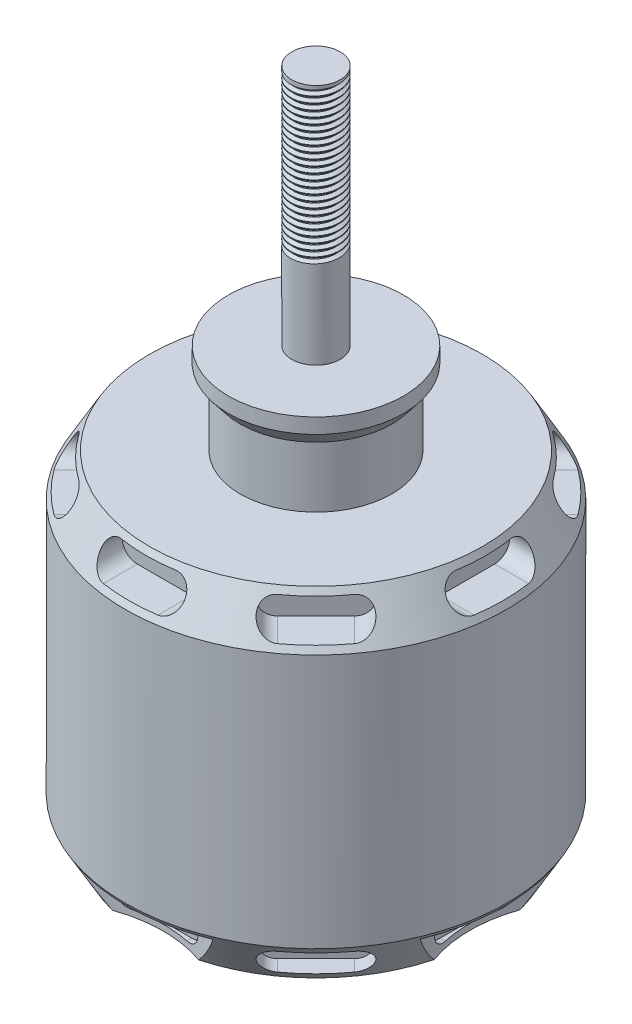
SolidWorks part; units mm, degrees
note: '?' marks a value the reader was unsure of.
ref_plane "Front Plane" through (0, 0, 0) normal (0, 0, 1) x (1, 0, 0)
ref_plane "Top Plane" through (0, 0, 0) normal (0, 1, 0) x (1, 0, 0)
ref_plane "Right Plane" through (0, 0, 0) normal (1, 0, 0) x (0, 0, -1)
sketch "Sketch1" plane through (0, 0, 0) normal (0, 1, 0) x (1, 0, 0)
  circle A0 centre (0, 0) radius 31.5
  dimension "D1" = 63
extrude "Boss-Extrude1" add sketch "Sketch1" along normal blind 40.7
ref_plane "Plane1" through (0, 47.7, 0) normal (0, 1, 0) x (1, 0, 0)
sketch "Sketch3" plane through (0, 47.7, 0) normal (0, 1, 0) x (1, 0, 0)
  circle A0 centre (0, 0) radius 27.5
  dimension "D1" = 55
loft "Loft1" add profiles "Sketch3" section "Sketch3" section edge at (0, 40.7, 31.5) connector at (-15.8974, 47.7, 22.4393) connector at (-17.8527, 40.7, 25.9525)
sketch "Sketch5" plane through (0, 47.7, 0) normal (0, 1, 0) x (1, 0, 0)
  circle A0 centre (0, 0) radius 12.5
  dimension "D1" = 25
extrude "Boss-Extrude2" add sketch "Sketch5" along normal blind 10
ref_plane "Plane3" through (0, 62.7, 0) normal (0, 1, 0) x (1, 0, 0)
sketch "Sketch8" plane through (0, 62.7, 0) normal (0, 1, 0) x (1, 0, 0)
  circle A0 centre (0, 0) radius 14.462
extrude "Boss-Extrude3" add sketch "Sketch8" against normal blind 2.5 separate body
loft "Loft3" add section edge at (0, 60.2, 14.462) section edge at (0, 57.7, 12.5) connector at (-8.5885, 60.2, 11.6356) connector at (-7.8828, 57.7, 9.7011)
sketch "Sketch9" plane through (0, 62.7, 0) normal (0, 1, 0) x (1, 0, 0)
  circle A0 centre (0, 0) radius 4
  dimension "D1" = 8
extrude "Boss-Extrude4" add sketch "Sketch9" along normal blind 40
thread "Thread1" pitch 1 method cut profile "Thread Profile1" start angle 0, offset 0, length 25, pitch 1, diameter 8
ref_plane "Plane4" through (-4, 102.7, 0) normal (0, 0, 1) x (-1, 0, 0)
sketch "Thread Profile1" plane through (-4, 102.7, 0) normal (0, 0, 1) x (-1, 0, 0)
  line L0 (0, 0) -> (0, 1) construction
  line L11 (0, 0) -> (0, 0.875)
  line L12 (0, 0.875) -> (-0.5413, 0.5625)
  line L13 (-0.5413, 0.5625) -> (-0.5413, 0.3125)
  line L15 (-0.5413, 0.3125) -> (0, 0)
  line L17 (-0.5413, 0.4375) -> (0, 0.4375) construction
  point P2 (0, 0)
  dimension "Pitch" = 1
  dimension "Profile_Angle" = 60
  dimension "Profile_Land" = 0.25
  dimension "Profile_Height" = 0.5413
sketch "Sketch17" plane through (0, 0, 0) normal (0, -1, 0) x (1, 0, 0)
  circle A0 centre (0, 0) radius 31.5
extrude "Boss-Extrude5" add sketch "Sketch17" along normal blind 1.3
ref_plane "Plane5" through (0, -8.3, 0) normal (0, -1, 0) x (-1, 0, 0)
sketch "Sketch18" plane through (0, -8.3, 0) normal (0, -1, 0) x (-1, 0, 0)
  circle A0 centre (0, 0) radius 27.5
  dimension "D1" = 55
loft "Loft4" add profiles "Sketch18" section "Sketch18" section edge at (0, -1.3, -31.5) connector at (25.19, -8.3, 11.0325) connector at (30.1075, -1.3, 9.2623)
sketch "Sketch20" plane through (0, -8.3, 0) normal (0, -1, 0) x (1, 0, 0)
  circle A0 centre (0, 0) radius 6.5
  dimension "D1" = 13
extrude "Boss-Extrude6" add sketch "Sketch20" along normal blind 0.75
sketch "Sketch21" plane through (0, -9.05, 0) normal (0, -1, 0) x (1, 0, 0)
  circle A0 centre (0, 0) radius 7
  dimension "D1" = 14
extrude "Boss-Extrude7" add sketch "Sketch21" along normal blind 5.55
sketch "Sketch23" plane through (0, -8.3, 0) normal (0, -1, 0) x (1, 0, 0)
  line L0 (0, 27.5) -> (0, -27.5) construction
  circle A0 centre (0, 0) radius 22 construction
  circle A1 centre (0, 0) radius 15 construction
  circle A2 centre (0, 0) radius 27.5 construction
  circle A3 centre (0, 22) radius 2
  circle A4 centre (0, 15) radius 2
  point P9 (0, 22)
  point P10 (19.0143, 27.2612)
  point P11 (30.1327, 31.5033)
  point P12 (25.788, 30.2375)
  point P14 (0, 22)
  dimension "D1" = 44
  dimension "D2" = 30
  dimension "D3" = 4
  dimension "D4" = 4
extrude "Cut-Extrude3" cut sketch "Sketch23" against normal blind 4
pattern_circular "CirPattern3" count 4 over 360 about axis through (0, 0, 0) along (0, 1, 0) of "Cut-Extrude3"
sketch "Sketch26" plane through (0, -8.3, 0) normal (0, -1, 0) x (1, 0, 0)
  line L0 (0, 31.5) -> (0, -27.5) construction
  line L1 (-12.0364, 29.1097) -> (-11.6051, 34.5401)
  line L2 (-11.6051, 34.5401) -> (12.9561, 30.5277)
  line L3 (12.9561, 30.5277) -> (11.9703, 28.9248)
  arc A0 (-12.0364, 29.1097) -> (11.9703, 28.9248) centre (0.1038, 46.7916) ccw
  circle A1 centre (0, 0) radius 31.5 construction
  circle A2 centre (0, 0) radius 27.5 construction
extrude "Cut-Extrude4" cut sketch "Sketch26" against normal blind 6.4
pattern_circular "CirPattern4" count 4 over 360 about axis through (0, 0, 0) along (0, 1, 0) of "Cut-Extrude4"
ref_plane "Plane6" through (0, -1.3, 0) normal (0, 1, 0) x (1, 0, 0)
ref_axis "Axis1" through (0, 108.565, 0) along (0, -1, 0)?
ref_plane "Plane8" through (0, 0, 0) normal (0.7071, 0, 0.7071) x (0, -1, 0)
ref_plane "Plane9" through (24.7487, 0, 24.7487) normal (0.7071, 0, 0.7071) x (0, -1, 0)
sketch "Sketch32" plane through (24.7487, 0, 24.7487) normal (0.7071, 0, 0.7071) x (0, -1, 0)
  line L0 (-44.2, -4.5) -> (-44.2, 4.5) construction
  line L3 (-47.7, 0) -> (14.6, 0) construction
  line L4 (-47.7, 12.5) -> (-47.7, -12.5) construction
  line L5 (14.6, -7) -> (14.6, 7) construction
  line L6 (-19.7, 31.5) -> (-19.7, -31.5) construction
  line L7 (1.3, 31.5) -> (-40.7, 31.5) construction
  line L8 (-40.7, -31.5) -> (1.3, -31.5) construction
  line L9 (-44.2, -29.5) -> (-44.2, 29.5) construction
  line L10 (-47.7, -27.5) -> (-40.7, -31.5) construction
  line L11 (-40.7, 31.5) -> (-47.7, 27.5) construction
  line L12 (-46.7, -4.5) -> (-46.7, 4.5)
  line L13 (-41.7, -4.5) -> (-41.7, 4.5)
  arc A2 (-46.7, -4.5) -> (-41.7, -4.5) centre (-44.2, -4.5) ccw
  arc A3 (-41.7, 4.5) -> (-46.7, 4.5) centre (-44.2, 4.5) ccw
  point P2 (-44.2, 0)
  dimension "D1" = 9
  dimension "D2" = 5
extrude "Cut-Extrude6" cut sketch "Sketch32" against normal blind 10
pattern_linear "LPattern1" count 2 spacing 49 along (0, -1, 0) of "Cut-Extrude6"
pattern_circular "CirPattern6" count 8 over 360 of "LPattern1", "Cut-Extrude6"
sketch "Sketch33" plane through (0, 62.7, 0) normal (0, 1, 0) x (1, 0, 0)
  circle A0 centre (0, 0) radius 203.2
  dimension "D1" = 406.4
